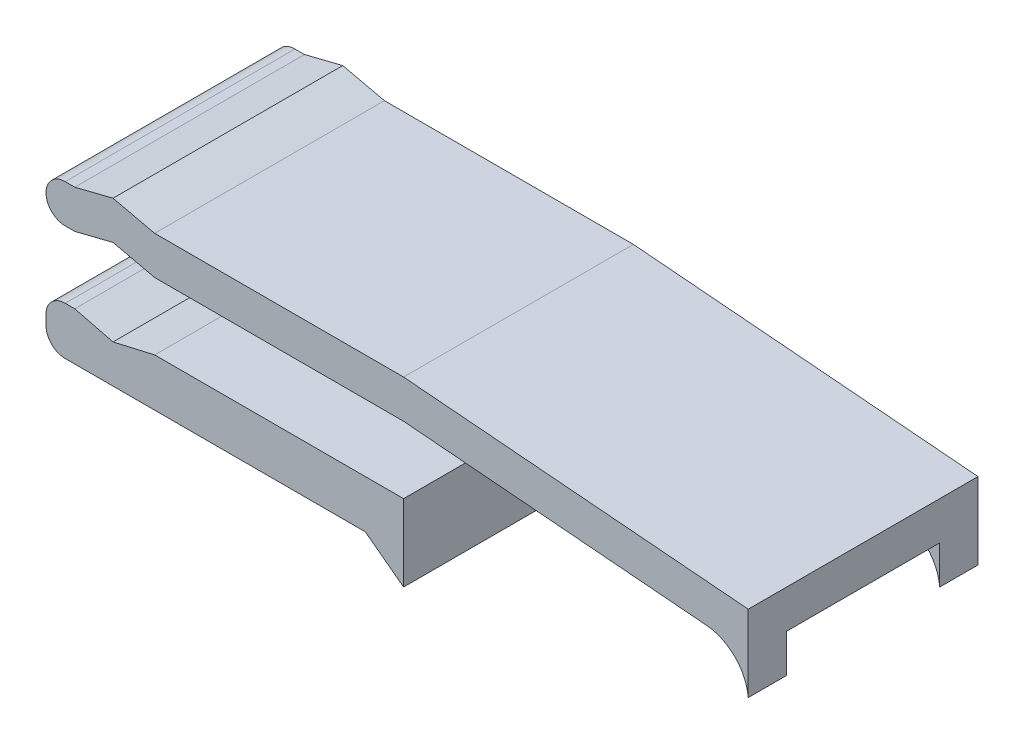
SolidWorks part; units mm, degrees
ref_plane "Front Plane" through (0, 0, 0) normal (0, 0, 1) x (1, 0, 0)
ref_plane "Top Plane" through (0, 0, 0) normal (0, 1, 0) x (1, 0, 0)
ref_plane "Right Plane" through (0, 0, 0) normal (1, 0, 0) x (0, 0, -1)
sketch "Sketch1" plane through (0, 0, 0) normal (0, 0, 1) x (1, 0, 0)
  line L0 (0, 0) -> (0, 4) construction
  line L1 (0, 0) -> (-18, 0) construction
  line L2 (0, 4) -> (-18, 5.5)
  line L3 (-18, 5.5) -> (-31, 5.5)
  line L4 (-31, 5.5) -> (-33.1759, 6)
  line L5 (-33.1759, 6) -> (-35.1759, 5.5)
  line L6 (-35.1759, 5.5) -> (-36.6759, 5.5)
  line L7 (-36.6759, 5.5) -> (-36.6759, 3.5)
  line L8 (-36.6759, -2.5) -> (-20, -2.5)
  line L9 (-20, -2.5) -> (-18, -4)
  line L10 (-36.6759, 3.5) -> (-35.1759, 3.5)
  line L11 (-35.1759, 3.5) -> (-33.1759, 4)
  line L12 (-18, 0) -> (-18, -4)
  line L13 (-18, 0) -> (-31, 0)
  line L14 (-31, 0) -> (-33.1759, -0.5)
  line L15 (-33.1759, -0.5) -> (-35.1759, 0)
  line L16 (-35.1759, 0) -> (-36.6759, 0)
  line L17 (-36.6759, 0) -> (-36.6759, -2.5)
  line L18 (-33.1759, 4) -> (-31, 3.5)
  line L19 (-31, 3.5) -> (-18, 3.5)
  line L20 (-18, 0) -> (-18, 5.5) construction
  line L21 (-18, 3.5) -> (0, 2)
  line L22 (0, 2) -> (0, 4)
  dimension "D1" = 13
  dimension "D2" = 18
  dimension "D3" = 0.5
  dimension "D4" = 2.5
  dimension "D5" = 1.5
  dimension "D6" = 3.5
  dimension "D8" = 2
  dimension "D9" = 0.5
  dimension "D10" = 2
  dimension "D11" = 0.5
  dimension "D12" = 2
  dimension "D13" = 2
  dimension "D15" = 4.1759
  dimension "D16" = 1.5
extrude "Boss-Extrude1" add sketch "Sketch1" along normal blind 12
sketch "Sketch2" plane through (0, -2.5, 0) normal (0, -1, 0) x (1, 0, 0)
  line L0 (-20, 12) -> (-20, 0) construction
  line L1 (-29, 8.5) -> (-23.5, 8.5)
  line L2 (-29, 8.5) -> (-29, 3.5)
  line L3 (-29, 3.5) -> (-23.5, 3.5)
  line L4 (-23.5, 8.5) -> (-23.5, 3.5)
  line L5 (-36.6759, 0) -> (-20, 0) construction
  dimension "D1" = 3.5
  dimension "D2" = 5.5
  dimension "D3" = 5
  dimension "D4" = 3.5
extrude "Cut-Extrude1" cut sketch "Sketch2" against normal blind 3
sketch "Sketch3" plane through (0, 0, 3.5) normal (0, 0, 1) x (1, 0, 0)
  line L0 (-23.5, 0) -> (-25.5, -2)
  line L1 (-25.5, -2) -> (-25.5, -2.5)
  line L2 (-36.6759, -2.5) -> (-20, -2.5) construction
  line L3 (-25.5, -2.5) -> (-23.5, -2.5)
  line L4 (-23.5, -2.5) -> (-23.5, 0)
  dimension "D1" = 0.5
  dimension "D2" = 2
extrude "Boss-Extrude2" add sketch "Sketch3" along normal up to surface (5 mm away) up to face at (-26.25, -1.25, 8.5)
sketch "Sketch4" plane through (0, 0, 12) normal (0, 0, 1) x (1, 0, 0)
  line L0 (-26.5, -2) -> (-24.5, 0)
  line L1 (-18, 0) -> (-31, 0) construction
  line L2 (-24.5, 0) -> (-24.5, 0.5)
  line L3 (-24.5, 0.5) -> (-26, 0.5)
  line L4 (-26, 0.5) -> (-26, 1)
  line L5 (-31, 3.5) -> (-18, 3.5) construction
  line L6 (-26.5, -2) -> (-26.5, -3)
  line L7 (-26.5, -3) -> (-27.5, -3)
  line L8 (-27.5, -3) -> (-27.5, 1)
  line L10 (-25.5, -2) -> (-25.5, -2.5) construction
  line L11 (-27, 3.5) -> (-24.5, 3.5)
  arc A0 (-26, 1) -> (-24.5, 3.5) centre (-23.1667, 1) cw
  arc A1 (-27.5, 1) -> (-27, 3.5) centre (-21, 1) cw
  dimension "D10" = 0.5
  dimension "D1" = 1.5
  dimension "D2" = 1
  dimension "D3" = 45
  dimension "D4" = 0.5
  dimension "D5" = 1
  dimension "D6" = 1
  dimension "D7" = 2
  dimension "D8" = 0.5
  dimension "D9" = 4
extrude "Boss-Extrude3" add sketch "Sketch4" against normal blind 4 from offset 4 offset against normal yes
fillet "Fillet7" radius 1 1 edges at (-36.6759, 0, 6)
fillet "Fillet8" radius 1 1 edges at (-36.6759, 3.5, 6)
fillet "Fillet10" radius 1 1 edges at (-36.6759, 5.5, 6)
fillet "Fillet11" radius 1 1 edges at (-36.6759, -2.5, 6)
fillet "Fillet12" radius 0.5 2 edges at (-27.5, -3, 6) (-26.5, -3, 6)
sketch "Sketch5" plane through (0, 0, 12) normal (0, 0, 1) x (1, 0, 0)
  line L0 (0, 2) -> (0, 0)
  line L1 (-18, 3.5) -> (0, 2) construction
  line L2 (-2.1818, 2.1818) -> (0, 2)
  arc A0 (-2.1818, 2.1818) -> (0, 0) centre (-2.3802, -0.1983) cw
extrude "Boss-Extrude4" add sketch "Sketch5" against normal blind 2
extrude "Boss-Extrude5" add sketch "Sketch5<2>" along normal blind 2 from offset 12 offset against normal yes
sketch "Sketch5<2>" plane through (0, 0, 12) normal (0, 0, 1) x (1, 0, 0) same geometry as "Sketch5"
